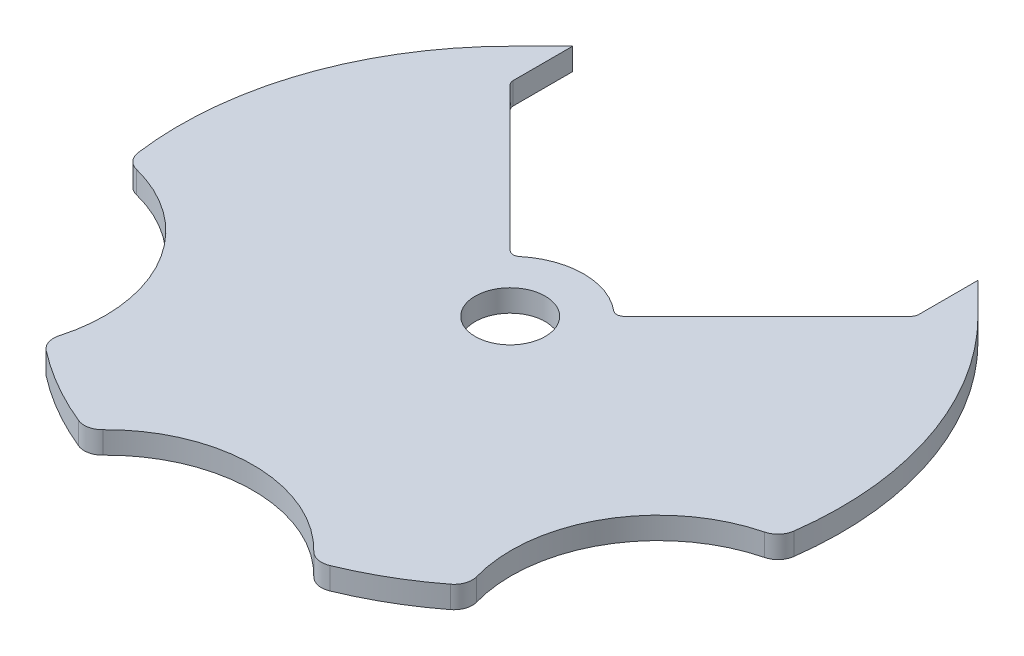
SolidWorks part; units mm, degrees
material "ABS"
ref_plane "Front Plane" through (0, 0, 0) normal (0, 0, 1) x (1, 0, 0)
ref_plane "Top Plane" through (0, 0, 0) normal (0, 1, 0) x (1, 0, 0)
ref_plane "Right Plane" through (0, 0, 0) normal (1, 0, 0) x (0, 0, -1)
sketch "Sketch1" plane through (0, 0, 0) normal (0, 1, 0) x (1, 0, 0)
  line L0 (-31.8198, 31.8198) -> (-7.0711, 7.0711)
  line L1 (7.0711, 7.0711) -> (31.8198, 31.8198)
  line L2 (0, 0) -> (0, 20) construction
  line L3 (0, 0) -> (-7.0711, 7.0711) construction
  line L4 (7.0711, 7.0711) -> (0, 0) construction
  arc A0 (-31.8198, 31.8198) -> (31.8198, 31.8198) centre (0, 0) ccw
  circle A1 centre (0, 0) radius 4.7625
  arc A2 (7.0711, 7.0711) -> (-7.0711, 7.0711) centre (0, 0) ccw
  dimension "D1" = 9.525
  dimension "D2" = 90
  dimension "D3" = 20
  dimension "D4" = 45
extrude "Boss-Extrude1" add sketch "Sketch1" along normal blind 3
sketch "Sketch2" plane through (0, 3, 0) normal (0, 1, 0) x (1, 0, 0)
  line L0 (4.0536, 2.5) -> (4.0536, -2.5)
  arc A0 (4.0536, -2.5) -> (4.0536, 2.5) centre (0, 0) ccw
  circle A1 centre (0, 0) radius 4.7625 construction
  dimension "D1" = 5
extrude "Shaft D" [suppressed] add sketch "Sketch2" against normal up to surface (10 mm away) up to face at (0, 0, -0.9727)
sketch "Sketch3" plane through (0, 3, 0) normal (0, 1, 0) x (1, 0, 0)
  line L0 (-31.8198, 31.8198) -> (-27.5772, 36.0624)
  line L1 (-27.5772, 36.0624) -> (-27.5772, 27.5772)
  line L2 (-7.0711, 7.0711) -> (-31.8198, 31.8198) construction
  line L3 (-27.5772, 27.5772) -> (-31.8198, 31.8198)
  line L4 (0, 0) -> (0, 30.6174) construction
  line L5 (27.5772, 27.5772) -> (31.8198, 31.8198)
  line L6 (27.5772, 36.0624) -> (27.5772, 27.5772)
  line L7 (31.8198, 31.8198) -> (27.5772, 36.0624)
  dimension "D1" = 6
extrude "Boss-Extrude2" add sketch "Sketch3" against normal up to surface (3 mm away) up to face at (0, 0, -0.9727)
fillet "Fillet1" radius 1 4 edges at (7.0711, 1.5, -7.0711) (-7.0711, 1.5, -7.0711) (27.5772, 1.5, -27.5772) (-27.5772, 1.5, -27.5772)
sketch "Sketch4" plane through (0, 3, 0) normal (0, 1, 0) x (1, 0, 0)
  line L0 (-47.6314, -27.5) -> (47.6314, -27.5) construction
  line L1 (47.6314, -27.5) -> (0, -55) construction
  line L2 (0, -55) -> (-47.6314, -27.5) construction
  line L3 (-47.6314, -27.5) -> (0, 0) construction
  line L4 (0, 0) -> (0, -55) construction
  line L5 (0, 0) -> (47.6314, -27.5) construction
  circle A0 centre (-47.6314, -27.5) radius 20
  circle A1 centre (47.6314, -27.5) radius 20
  circle A2 centre (0, -55) radius 20
  point P6 (0, -27.5)
  dimension "D1" = 40
  dimension "D2" = 60
  dimension "D3" = 55
extrude "Cut-Extrude1" cut sketch "Sketch4" against normal blind 10
fillet "Fillet2" radius 2.5 6 edges at (44.3231, 1.5, 7.7755) (28.8954, 1.5, 34.4972) (15.4278, 1.5, 42.2727) (-15.4278, 1.5, 42.2727) (-28.8954, 1.5, 34.4972) (-44.3231, 1.5, 7.7755)
